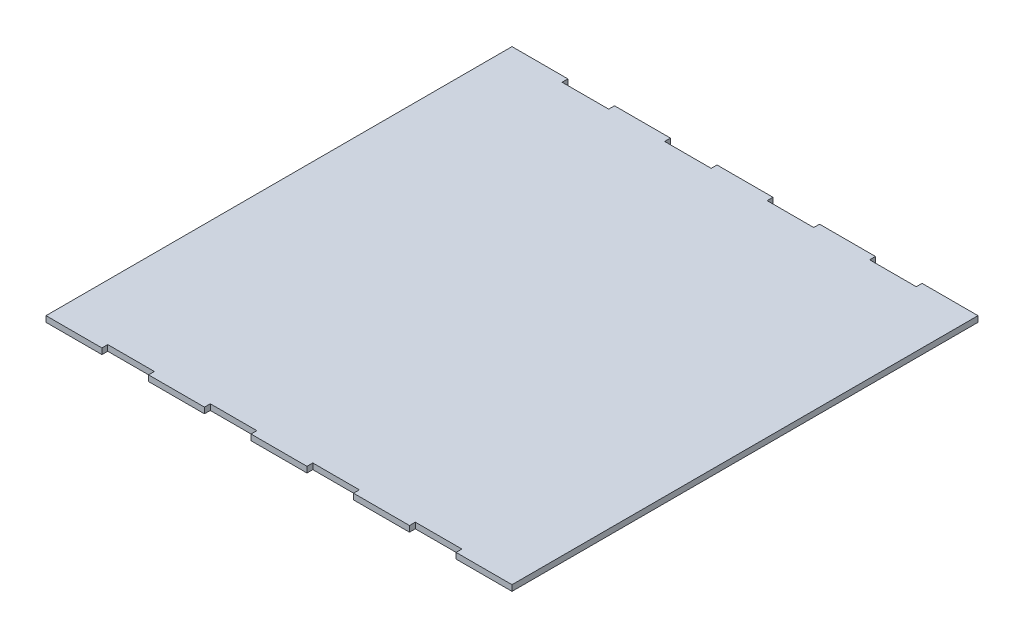
SolidWorks part; units mm, degrees
ref_plane "Front" through (0, 0, 0) normal (0, 0, 1) x (1, 0, 0)
ref_plane "Top" through (0, 0, 0) normal (0, 1, 0) x (1, 0, 0)
ref_plane "Right" through (0, 0, 0) normal (1, 0, 0) x (0, 0, -1)
sketch "Skizze1" plane through (0, 0, 0) normal (0, 1, 0) x (1, 0, 0)
  line L1 (200, 200) -> (-200, 200)
  line L2 (200, 200) -> (200, -200)
  line L3 (200, -200) -> (-200, -200)
  line L4 (-200, 200) -> (-200, -200)
  line L5 (200, 200) -> (-200, -200) construction
  line L6 (200, -200) -> (-200, 200) construction
  point P0 (0, 0)
  dimension "D1" = 400
  dimension "D2" = 400
extrude "Grundplatte" add sketch "Skizze1" along normal blind 5
ref_plane "Ebene1" through (0, 0, 0) normal (0, 0, 1) x (1, 0, 0)
ref_plane "Ebene2" through (0, 0, 0) normal (-1, 0, 0) x (0, 0, 1)
sketch "Skizze2" plane through (0, 5, 0) normal (0, 1, 0) x (1, 0, 0)
  line L0 (-200, 200) -> (-200, -200) construction
  line L5 (0, 200) -> (0, 0) construction
  line L6 (200, 200) -> (-200, 200) construction
  line L7 (152, 195) -> (200, 195) construction
  line L8 (24, 195) -> (-24, 195) construction
  line L13 (-152, 200) -> (-112, 200)
  line L14 (-152, 200) -> (-152, 195)
  line L15 (-152, 195) -> (-112, 195)
  line L16 (-112, 200) -> (-112, 195)
  line L17 (-64, 200) -> (-24, 200)
  line L18 (-64, 200) -> (-64, 195)
  line L19 (-64, 195) -> (-24, 195)
  line L20 (-24, 200) -> (-24, 195)
  line L21 (-64, 195) -> (-112, 195) construction
  line L22 (-152, 195) -> (-200, 195) construction
  line L23 (64, 195) -> (112, 195) construction
  line L24 (24, 200) -> (24, 195)
  line L25 (64, 195) -> (24, 195)
  line L42 (64, 200) -> (64, 195)
  line L43 (64, 200) -> (24, 200)
  line L44 (112, 200) -> (112, 195)
  line L45 (152, 195) -> (112, 195)
  line L46 (152, 200) -> (152, 195)
  line L63 (152, 200) -> (112, 200)
  point P12 (0, 195)
  dimension "D1" = 40
  dimension "D2" = 5
extrude "Schnitt-Linear austragen1" cut sketch "Skizze2" against normal through all
mirror "Spiegeln1" about plane through (0, 0, 0) normal (0, 0, 1) of "Schnitt-Linear austragen1"
ref_axis "Achse1" through (0, 10.2665, 0) along (0, -1, 0)
pattern_circular "Kreismuster1" [suppressed] count 2 over 90 about axis through (0, 10.2665, 0) along (0, -1, 0) of bodies 103
